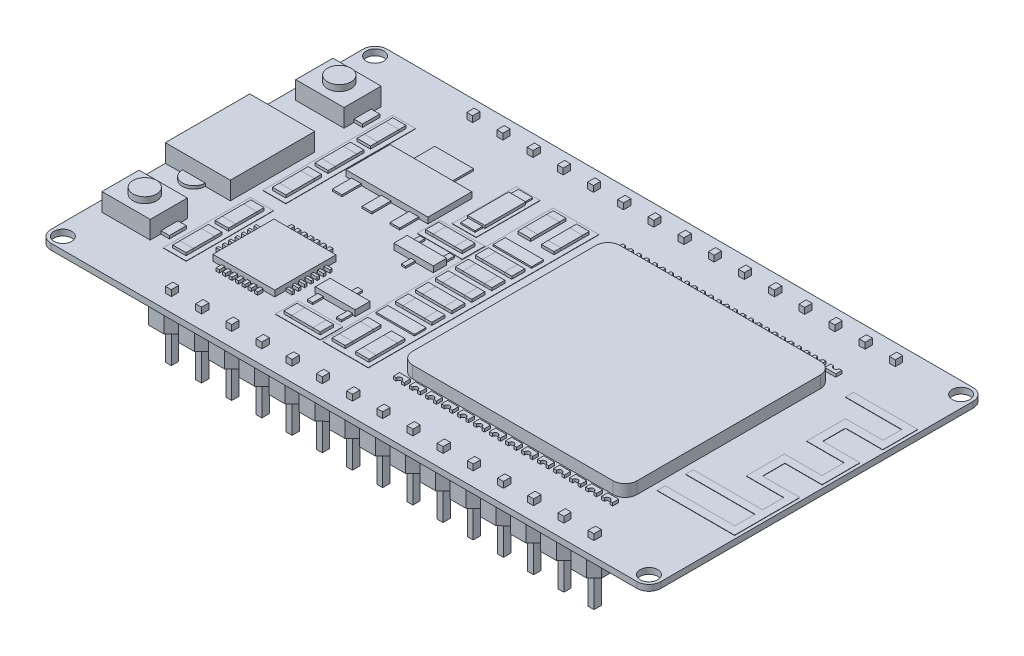
SolidWorks part; units mm, degrees
ref_plane "Front Plane" through (0, 0, 0) normal (0, 0, 1) x (1, 0, 0)
ref_plane "Top Plane" through (0, 0, 0) normal (0, 1, 0) x (1, 0, 0)
ref_plane "Right Plane" through (0, 0, 0) normal (1, 0, 0) x (0, 0, -1)
sketch "Sketch1" plane through (0, 0, 0) normal (0, 1, 0) x (1, 0, 0)
  line L0 (166.6667, 275.5) -> (833.3333, 275.5) construction
sketch "Sketch2" plane through (0, 0, 0) normal (0, 1, 0) x (1, 0, 0)
  line L1 (0, 0) -> (25.5, 0)
  line L2 (0, 0) -> (0, 14.05)
  line L3 (0, 14.05) -> (25.5, 14.05)
  line L4 (25.5, 0) -> (25.5, 14.05)
  dimension "D1" = 14.05
  dimension "D2" = 25.5
extrude "Boss-Extrude1" add sketch "Sketch2" against normal blind 0.5
fillet "Fillet3" radius 1 1 edges at (0, -0.25, 0)
sketch "Sketch3" plane through (0, 0, 0) normal (0, 1, 0) x (1, 0, 0)
  line L0 (0.2929, 0.2929) -> (1, 1) construction
  arc A0 (0, 1) -> (1, 0) centre (1, 1) ccw construction
  circle A1 centre (1, 1) radius 0.7368
extrude "Cut-Extrude1" cut sketch "Sketch3" along normal up to surface (-0.5 mm away) up to face at (10.3586, -0.5, -5.7786)
mirror "Mirror1" about plane through (25.5, -0.5, 0) normal (1, 0, 0) of bodies 102
mirror "Mirror2" about plane through (0, -0.5, -14.05) normal (0, 0, -1) of bodies 103
sketch "Sketch4" plane through (0, 0, 0) normal (0, 1, 0) x (1, 0, 0)
  line L1 (25.9436, 22.6267) -> (42.7039, 22.6267)
  line L2 (24.9436, 21.6267) -> (24.9436, 6.2994)
  line L3 (25.9436, 5.2994) -> (42.7039, 5.2994)
  line L4 (43.7039, 21.6267) -> (43.7039, 6.2994)
  arc A0 (24.9436, 6.2994) -> (25.9436, 5.2994) centre (25.9436, 6.2994) ccw
  arc A1 (42.7039, 5.2994) -> (43.7039, 6.2994) centre (42.7039, 6.2994) ccw
  arc A2 (42.7039, 22.6267) -> (43.7039, 21.6267) centre (42.7039, 21.6267) cw
  arc A3 (25.9436, 22.6267) -> (24.9436, 21.6267) centre (25.9436, 21.6267) ccw
  dimension "D1" = 1
extrude "Boss-Extrude2" add sketch "Sketch4" along normal blind 1 separate body
sketch "Sketch5" plane through (0, 0, 0) normal (0, 1, 0) x (1, 0, 0)
  line L0 (24.7912, 7.6997) -> (24.2806, 7.6997)
  line L1 (24.2806, 7.6997) -> (24.2806, 7.8949)
  line L2 (24.7912, 7.6997) -> (24.7912, 8.5161)
  line L4 (24.2806, 8.5161) -> (24.2806, 8.3221)
  line L5 (24.7912, 8.5161) -> (24.2806, 8.5161)
  line L6 (24.2806, 9.8562) -> (24.2806, 9.6622)
  line L7 (24.7912, 9.8562) -> (24.2806, 9.8562)
  line L8 (24.7912, 9.0397) -> (24.7912, 9.8562)
  line L9 (24.7912, 9.0397) -> (24.2806, 9.0397)
  line L10 (24.2806, 9.0397) -> (24.2806, 9.235)
  line L11 (24.2806, 11.1963) -> (24.2806, 11.0023)
  line L12 (24.7912, 11.1963) -> (24.2806, 11.1963)
  line L13 (24.7912, 10.3798) -> (24.7912, 11.1963)
  line L14 (24.7912, 10.3798) -> (24.2806, 10.3798)
  line L15 (24.2806, 10.3798) -> (24.2806, 10.575)
  line L16 (24.2806, 12.5363) -> (24.2806, 12.3423)
  line L17 (24.7912, 12.5363) -> (24.2806, 12.5363)
  line L18 (24.7912, 11.7199) -> (24.7912, 12.5363)
  line L19 (24.7912, 11.7199) -> (24.2806, 11.7199)
  line L20 (24.2806, 11.7199) -> (24.2806, 11.9151)
  line L21 (24.2806, 13.8764) -> (24.2806, 13.6824)
  line L22 (24.7912, 13.8764) -> (24.2806, 13.8764)
  line L23 (24.7912, 13.06) -> (24.7912, 13.8764)
  line L24 (24.7912, 13.06) -> (24.2806, 13.06)
  line L25 (24.2806, 13.06) -> (24.2806, 13.2552)
  line L26 (24.2806, 15.2165) -> (24.2806, 15.0225)
  line L27 (24.7912, 15.2165) -> (24.2806, 15.2165)
  line L28 (24.7912, 14.4) -> (24.7912, 15.2165)
  line L29 (24.7912, 14.4) -> (24.2806, 14.4)
  line L30 (24.2806, 14.4) -> (24.2806, 14.5953)
  line L31 (24.2806, 16.5566) -> (24.2806, 16.3626)
  line L32 (24.7912, 16.5566) -> (24.2806, 16.5566)
  line L33 (24.7912, 15.7401) -> (24.7912, 16.5566)
  line L34 (24.7912, 15.7401) -> (24.2806, 15.7401)
  line L35 (24.2806, 15.7401) -> (24.2806, 15.9353)
  line L36 (24.2806, 17.8967) -> (24.2806, 17.7026)
  line L37 (24.7912, 17.8967) -> (24.2806, 17.8967)
  line L38 (24.7912, 17.0802) -> (24.7912, 17.8967)
  line L39 (24.7912, 17.0802) -> (24.2806, 17.0802)
  line L40 (24.2806, 17.0802) -> (24.2806, 17.2754)
  line L41 (24.2806, 19.2367) -> (24.2806, 19.0427)
  line L42 (24.7912, 19.2367) -> (24.2806, 19.2367)
  line L43 (24.7912, 18.4203) -> (24.7912, 19.2367)
  line L44 (24.7912, 18.4203) -> (24.2806, 18.4203)
  line L45 (24.2806, 18.4203) -> (24.2806, 18.6155)
  line L46 (24.2806, 20.5768) -> (24.2806, 20.3828)
  line L47 (24.7912, 20.5768) -> (24.2806, 20.5768)
  line L48 (24.7912, 19.7603) -> (24.7912, 20.5768)
  line L49 (24.7912, 19.7603) -> (24.2806, 19.7603)
  line L50 (24.2806, 19.7603) -> (24.2806, 19.9556)
  line L51 (25.1907, 23.6105) -> (25.1907, 23.1041)
  line L52 (25.1907, 23.1041) -> (26.111, 23.1041)
  line L54 (25.1907, 23.6105) -> (25.4208, 23.6105)
  line L55 (26.111, 23.6105) -> (26.111, 23.1041)
  line L56 (26.111, 23.6105) -> (25.8809, 23.6105)
  line L57 (26.5297, 23.1041) -> (27.45, 23.1041)
  line L58 (27.45, 23.6105) -> (27.45, 23.1041)
  line L59 (27.45, 23.6105) -> (27.2199, 23.6105)
  line L60 (26.5297, 23.6105) -> (26.7598, 23.6105)
  line L61 (26.5297, 23.6105) -> (26.5297, 23.1041)
  line L62 (27.8686, 23.1041) -> (28.7889, 23.1041)
  line L63 (28.7889, 23.6105) -> (28.7889, 23.1041)
  line L64 (28.7889, 23.6105) -> (28.5589, 23.6105)
  line L65 (27.8686, 23.6105) -> (28.0987, 23.6105)
  line L66 (27.8686, 23.6105) -> (27.8686, 23.1041)
  line L67 (29.2076, 23.1041) -> (30.1279, 23.1041)
  line L68 (30.1279, 23.6105) -> (30.1279, 23.1041)
  line L69 (30.1279, 23.6105) -> (29.8978, 23.6105)
  line L70 (29.2076, 23.6105) -> (29.4377, 23.6105)
  line L71 (29.2076, 23.6105) -> (29.2076, 23.1041)
  line L72 (30.5466, 23.1041) -> (31.4669, 23.1041)
  line L73 (31.4669, 23.6105) -> (31.4669, 23.1041)
  line L74 (31.4669, 23.6105) -> (31.2368, 23.6105)
  line L75 (30.5466, 23.6105) -> (30.7766, 23.6105)
  line L76 (30.5466, 23.6105) -> (30.5466, 23.1041)
  line L77 (31.8855, 23.1041) -> (32.8058, 23.1041)
  line L78 (32.8058, 23.6105) -> (32.8058, 23.1041)
  line L79 (32.8058, 23.6105) -> (32.5758, 23.6105)
  line L80 (31.8855, 23.6105) -> (32.1156, 23.6105)
  line L81 (31.8855, 23.6105) -> (31.8855, 23.1041)
  line L82 (33.2245, 23.1041) -> (34.1448, 23.1041)
  line L83 (34.1448, 23.6105) -> (34.1448, 23.1041)
  line L84 (34.1448, 23.6105) -> (33.9147, 23.6105)
  line L85 (33.2245, 23.6105) -> (33.4546, 23.6105)
  line L86 (33.2245, 23.6105) -> (33.2245, 23.1041)
  line L87 (34.5635, 23.1041) -> (35.4838, 23.1041)
  line L88 (35.4838, 23.6105) -> (35.4838, 23.1041)
  line L89 (35.4838, 23.6105) -> (35.2537, 23.6105)
  line L90 (34.5635, 23.6105) -> (34.7935, 23.6105)
  line L91 (34.5635, 23.6105) -> (34.5635, 23.1041)
  line L92 (35.9024, 23.1041) -> (36.8227, 23.1041)
  line L93 (36.8227, 23.6105) -> (36.8227, 23.1041)
  line L94 (36.8227, 23.6105) -> (36.5926, 23.6105)
  line L95 (35.9024, 23.6105) -> (36.1325, 23.6105)
  line L96 (35.9024, 23.6105) -> (35.9024, 23.1041)
  line L97 (37.2414, 23.1041) -> (38.1617, 23.1041)
  line L98 (38.1617, 23.6105) -> (38.1617, 23.1041)
  line L99 (38.1617, 23.6105) -> (37.9316, 23.6105)
  line L100 (37.2414, 23.6105) -> (37.4715, 23.6105)
  line L101 (37.2414, 23.6105) -> (37.2414, 23.1041)
  line L102 (38.5803, 23.1041) -> (39.5006, 23.1041)
  line L103 (39.5006, 23.6105) -> (39.5006, 23.1041)
  line L104 (39.5006, 23.6105) -> (39.2706, 23.6105)
  line L105 (38.5803, 23.6105) -> (38.8104, 23.6105)
  line L106 (38.5803, 23.6105) -> (38.5803, 23.1041)
  line L107 (39.9193, 23.1041) -> (40.8396, 23.1041)
  line L108 (40.8396, 23.6105) -> (40.8396, 23.1041)
  line L109 (40.8396, 23.6105) -> (40.6095, 23.6105)
  line L110 (39.9193, 23.6105) -> (40.1494, 23.6105)
  line L111 (39.9193, 23.6105) -> (39.9193, 23.1041)
  line L112 (41.2583, 23.1041) -> (42.1786, 23.1041)
  line L113 (42.1786, 23.6105) -> (42.1786, 23.1041)
  line L114 (42.1786, 23.6105) -> (41.9485, 23.6105)
  line L115 (41.2583, 23.6105) -> (41.4883, 23.6105)
  line L116 (41.2583, 23.6105) -> (41.2583, 23.1041)
  line L117 (42.5972, 23.1041) -> (43.5175, 23.1041)
  line L118 (43.5175, 23.6105) -> (43.5175, 23.1041)
  line L119 (43.5175, 23.6105) -> (43.2875, 23.6105)
  line L120 (42.5972, 23.6105) -> (42.8273, 23.6105)
  line L121 (42.5972, 23.6105) -> (42.5972, 23.1041)
  line L123 (24.7912, 14.0286) -> (43.0574, 14.0286) construction
  line L124 (35.9024, 4.4466) -> (35.9024, 4.953)
  line L125 (35.9024, 4.4466) -> (36.1325, 4.4466)
  line L126 (36.8227, 4.4466) -> (36.5926, 4.4466)
  line L127 (36.8227, 4.4466) -> (36.8227, 4.953)
  line L128 (35.9024, 4.953) -> (36.8227, 4.953)
  line L129 (37.2414, 4.4466) -> (37.2414, 4.953)
  line L130 (37.2414, 4.4466) -> (37.4715, 4.4466)
  line L131 (38.1617, 4.4466) -> (37.9316, 4.4466)
  line L132 (38.1617, 4.4466) -> (38.1617, 4.953)
  line L133 (37.2414, 4.953) -> (38.1617, 4.953)
  line L134 (38.5803, 4.4466) -> (38.5803, 4.953)
  line L135 (38.5803, 4.4466) -> (38.8104, 4.4466)
  line L136 (39.5006, 4.4466) -> (39.2706, 4.4466)
  line L137 (39.5006, 4.4466) -> (39.5006, 4.953)
  line L138 (38.5803, 4.953) -> (39.5006, 4.953)
  line L139 (39.9193, 4.4466) -> (39.9193, 4.953)
  line L140 (39.9193, 4.4466) -> (40.1494, 4.4466)
  line L141 (40.8396, 4.4466) -> (40.6095, 4.4466)
  line L142 (40.8396, 4.4466) -> (40.8396, 4.953)
  line L143 (39.9193, 4.953) -> (40.8396, 4.953)
  line L144 (41.2583, 4.4466) -> (41.2583, 4.953)
  line L145 (41.2583, 4.4466) -> (41.4883, 4.4466)
  line L146 (42.1786, 4.4466) -> (41.9485, 4.4466)
  line L147 (42.1786, 4.4466) -> (42.1786, 4.953)
  line L148 (41.2583, 4.953) -> (42.1786, 4.953)
  line L149 (42.5972, 4.4466) -> (42.5972, 4.953)
  line L150 (42.5972, 4.4466) -> (42.8273, 4.4466)
  line L151 (43.5175, 4.4466) -> (43.2875, 4.4466)
  line L152 (43.5175, 4.4466) -> (43.5175, 4.953)
  line L153 (42.5972, 4.953) -> (43.5175, 4.953)
  line L154 (34.5635, 4.4466) -> (34.5635, 4.953)
  line L155 (34.5635, 4.4466) -> (34.7935, 4.4466)
  line L156 (35.4838, 4.4466) -> (35.2537, 4.4466)
  line L157 (35.4838, 4.4466) -> (35.4838, 4.953)
  line L158 (34.5635, 4.953) -> (35.4838, 4.953)
  line L159 (33.2245, 4.4466) -> (33.2245, 4.953)
  line L160 (33.2245, 4.4466) -> (33.4546, 4.4466)
  line L161 (34.1448, 4.4466) -> (33.9147, 4.4466)
  line L162 (34.1448, 4.4466) -> (34.1448, 4.953)
  line L163 (33.2245, 4.953) -> (34.1448, 4.953)
  line L164 (31.8855, 4.4466) -> (31.8855, 4.953)
  line L165 (31.8855, 4.4466) -> (32.1156, 4.4466)
  line L166 (32.8058, 4.4466) -> (32.5758, 4.4466)
  line L167 (32.8058, 4.4466) -> (32.8058, 4.953)
  line L168 (31.8855, 4.953) -> (32.8058, 4.953)
  line L169 (30.5466, 4.4466) -> (30.5466, 4.953)
  line L170 (30.5466, 4.4466) -> (30.7766, 4.4466)
  line L171 (31.4669, 4.4466) -> (31.2368, 4.4466)
  line L172 (31.4669, 4.4466) -> (31.4669, 4.953)
  line L173 (30.5466, 4.953) -> (31.4669, 4.953)
  line L174 (29.2076, 4.4466) -> (29.2076, 4.953)
  line L175 (29.2076, 4.4466) -> (29.4377, 4.4466)
  line L176 (30.1279, 4.4466) -> (29.8978, 4.4466)
  line L177 (30.1279, 4.4466) -> (30.1279, 4.953)
  line L178 (29.2076, 4.953) -> (30.1279, 4.953)
  line L179 (27.8686, 4.4466) -> (27.8686, 4.953)
  line L180 (27.8686, 4.4466) -> (28.0987, 4.4466)
  line L181 (28.7889, 4.4466) -> (28.5589, 4.4466)
  line L182 (28.7889, 4.4466) -> (28.7889, 4.953)
  line L183 (27.8686, 4.953) -> (28.7889, 4.953)
  line L184 (26.5297, 4.4466) -> (26.5297, 4.953)
  line L185 (26.5297, 4.4466) -> (26.7598, 4.4466)
  line L186 (27.45, 4.4466) -> (27.2199, 4.4466)
  line L187 (27.45, 4.4466) -> (27.45, 4.953)
  line L188 (26.5297, 4.953) -> (27.45, 4.953)
  line L189 (25.1907, 4.4466) -> (25.1907, 4.953)
  line L190 (25.1907, 4.4466) -> (25.4208, 4.4466)
  line L191 (26.111, 4.4466) -> (25.8809, 4.4466)
  line L192 (26.111, 4.4466) -> (26.111, 4.953)
  line L193 (25.1907, 4.953) -> (26.111, 4.953)
  arc A0 (24.2806, 7.8949) -> (24.2806, 8.3221) centre (24.2806, 8.1085) ccw
  arc A1 (24.2806, 9.235) -> (24.2806, 9.6622) centre (24.2806, 9.4486) ccw
  arc A2 (24.2806, 10.575) -> (24.2806, 11.0023) centre (24.2806, 10.7886) ccw
  arc A3 (24.2806, 11.9151) -> (24.2806, 12.3423) centre (24.2806, 12.1287) ccw
  arc A4 (24.2806, 13.2552) -> (24.2806, 13.6824) centre (24.2806, 13.4688) ccw
  arc A5 (24.2806, 14.5953) -> (24.2806, 15.0225) centre (24.2806, 14.8089) ccw
  arc A6 (24.2806, 15.9353) -> (24.2806, 16.3626) centre (24.2806, 16.149) ccw
  arc A7 (24.2806, 17.2754) -> (24.2806, 17.7026) centre (24.2806, 17.489) ccw
  arc A8 (24.2806, 18.6155) -> (24.2806, 19.0427) centre (24.2806, 18.8291) ccw
  arc A9 (24.2806, 19.9556) -> (24.2806, 20.3828) centre (24.2806, 20.1692) ccw
  arc A10 (25.4208, 23.6105) -> (25.8809, 23.6105) centre (25.6509, 23.6105) ccw
  arc A11 (26.7598, 23.6105) -> (27.2199, 23.6105) centre (26.9898, 23.6105) ccw
  arc A12 (28.0987, 23.6105) -> (28.5589, 23.6105) centre (28.3288, 23.6105) ccw
  arc A13 (29.4377, 23.6105) -> (29.8978, 23.6105) centre (29.6678, 23.6105) ccw
  arc A14 (30.7766, 23.6105) -> (31.2368, 23.6105) centre (31.0067, 23.6105) ccw
  arc A15 (32.1156, 23.6105) -> (32.5758, 23.6105) centre (32.3457, 23.6105) ccw
  arc A16 (33.4546, 23.6105) -> (33.9147, 23.6105) centre (33.6846, 23.6105) ccw
  arc A17 (34.7935, 23.6105) -> (35.2537, 23.6105) centre (35.0236, 23.6105) ccw
  arc A18 (36.1325, 23.6105) -> (36.5926, 23.6105) centre (36.3626, 23.6105) ccw
  arc A19 (37.4715, 23.6105) -> (37.9316, 23.6105) centre (37.7015, 23.6105) ccw
  arc A20 (38.8104, 23.6105) -> (39.2706, 23.6105) centre (39.0405, 23.6105) ccw
  arc A21 (40.1494, 23.6105) -> (40.6095, 23.6105) centre (40.3795, 23.6105) ccw
  arc A22 (41.4883, 23.6105) -> (41.9485, 23.6105) centre (41.7184, 23.6105) ccw
  arc A23 (42.8273, 23.6105) -> (43.2875, 23.6105) centre (43.0574, 23.6105) ccw
  arc A24 (36.1325, 4.4466) -> (36.5926, 4.4466) centre (36.3626, 4.4466) cw
  arc A25 (37.4715, 4.4466) -> (37.9316, 4.4466) centre (37.7015, 4.4466) cw
  arc A26 (38.8104, 4.4466) -> (39.2706, 4.4466) centre (39.0405, 4.4466) cw
  arc A27 (40.1494, 4.4466) -> (40.6095, 4.4466) centre (40.3795, 4.4466) cw
  arc A28 (41.4883, 4.4466) -> (41.9485, 4.4466) centre (41.7184, 4.4466) cw
  arc A29 (42.8273, 4.4466) -> (43.2875, 4.4466) centre (43.0574, 4.4466) cw
  arc A30 (34.7935, 4.4466) -> (35.2537, 4.4466) centre (35.0236, 4.4466) cw
  arc A31 (33.4546, 4.4466) -> (33.9147, 4.4466) centre (33.6846, 4.4466) cw
  arc A32 (32.1156, 4.4466) -> (32.5758, 4.4466) centre (32.3457, 4.4466) cw
  arc A33 (30.7766, 4.4466) -> (31.2368, 4.4466) centre (31.0067, 4.4466) cw
  arc A34 (29.4377, 4.4466) -> (29.8978, 4.4466) centre (29.6678, 4.4466) cw
  arc A35 (28.0987, 4.4466) -> (28.5589, 4.4466) centre (28.3288, 4.4466) cw
  arc A36 (26.7598, 4.4466) -> (27.2199, 4.4466) centre (26.9898, 4.4466) cw
  arc A37 (25.4208, 4.4466) -> (25.8809, 4.4466) centre (25.6509, 4.4466) cw
  dimension "D1" = 10
  dimension "D2" = 14
extrude "Boss-Extrude3" add sketch "Sketch5" along normal blind 0.25 separate body
sketch "Sketch6" plane through (0, 0, 0) normal (0, 1, 0) x (1, 0, 0)
  line L1 (9.0736, 10.5768) -> (14.253, 10.5768)
  line L2 (9.0736, 10.5768) -> (9.0736, 5.4648)
  line L3 (9.0736, 5.4648) -> (14.253, 5.4648)
  line L4 (14.253, 10.5768) -> (14.253, 5.4648)
extrude "Boss-Extrude4" add sketch "Sketch6" along normal blind 0.5 separate body
sketch "Sketch7" plane through (0, 0, 0) normal (0, 1, 0) x (1, 0, 0)
  line L0 (14.3341, 7.051) -> (14.3341, 6.8485)
  line L1 (14.3341, 6.525) -> (14.8378, 6.525)
  line L2 (14.3341, 6.525) -> (14.3341, 6.3225)
  line L3 (14.3341, 6.3225) -> (14.8378, 6.3225)
  line L4 (14.8378, 6.525) -> (14.8378, 6.3225)
  line L5 (14.3341, 7.051) -> (14.8378, 7.051)
  line L6 (14.8378, 7.051) -> (14.8378, 6.8485)
  line L7 (14.3341, 6.8485) -> (14.8378, 6.8485)
  line L8 (14.3341, 7.5771) -> (14.3341, 7.3746)
  line L9 (14.3341, 7.5771) -> (14.8378, 7.5771)
  line L10 (14.8378, 7.5771) -> (14.8378, 7.3746)
  line L11 (14.3341, 7.3746) -> (14.8378, 7.3746)
  line L12 (14.3341, 8.1031) -> (14.3341, 7.9006)
  line L13 (14.3341, 8.1031) -> (14.8378, 8.1031)
  line L14 (14.8378, 8.1031) -> (14.8378, 7.9006)
  line L15 (14.3341, 7.9006) -> (14.8378, 7.9006)
  line L16 (14.3341, 8.6292) -> (14.3341, 8.4267)
  line L17 (14.3341, 8.6292) -> (14.8378, 8.6292)
  line L18 (14.8378, 8.6292) -> (14.8378, 8.4267)
  line L19 (14.3341, 8.4267) -> (14.8378, 8.4267)
  line L20 (14.3341, 9.1552) -> (14.3341, 8.9527)
  line L21 (14.3341, 9.1552) -> (14.8378, 9.1552)
  line L22 (14.8378, 9.1552) -> (14.8378, 8.9527)
  line L23 (14.3341, 8.9527) -> (14.8378, 8.9527)
  line L24 (14.3341, 9.6813) -> (14.3341, 9.4788)
  line L25 (14.3341, 9.6813) -> (14.8378, 9.6813)
  line L26 (14.8378, 9.6813) -> (14.8378, 9.4788)
  line L27 (14.3341, 9.4788) -> (14.8378, 9.4788)
  line L28 (11.6633, 10.5768) -> (11.6633, 5.4648) construction
  line L29 (14.253, 10.5768) -> (9.0736, 10.5768) construction
  line L30 (9.0736, 5.4648) -> (14.253, 5.4648) construction
  line L31 (8.9924, 6.3225) -> (8.4887, 6.3225)
  line L32 (8.4887, 6.525) -> (8.4887, 6.3225)
  line L33 (8.9924, 6.525) -> (8.4887, 6.525)
  line L34 (8.9924, 6.525) -> (8.9924, 6.3225)
  line L35 (8.9924, 7.051) -> (8.4887, 7.051)
  line L36 (8.4887, 7.051) -> (8.4887, 6.8485)
  line L37 (8.9924, 6.8485) -> (8.4887, 6.8485)
  line L38 (8.9924, 7.051) -> (8.9924, 6.8485)
  line L39 (8.9924, 7.5771) -> (8.4887, 7.5771)
  line L40 (8.4887, 7.5771) -> (8.4887, 7.3746)
  line L41 (8.9924, 7.3746) -> (8.4887, 7.3746)
  line L42 (8.9924, 7.5771) -> (8.9924, 7.3746)
  line L43 (8.9924, 8.1031) -> (8.4887, 8.1031)
  line L44 (8.4887, 8.1031) -> (8.4887, 7.9006)
  line L45 (8.9924, 7.9006) -> (8.4887, 7.9006)
  line L46 (8.9924, 8.1031) -> (8.9924, 7.9006)
  line L47 (8.9924, 8.6292) -> (8.4887, 8.6292)
  line L48 (8.4887, 8.6292) -> (8.4887, 8.4267)
  line L49 (8.9924, 8.4267) -> (8.4887, 8.4267)
  line L50 (8.9924, 8.6292) -> (8.9924, 8.4267)
  line L51 (8.9924, 9.1552) -> (8.4887, 9.1552)
  line L52 (8.4887, 9.1552) -> (8.4887, 8.9527)
  line L53 (8.9924, 8.9527) -> (8.4887, 8.9527)
  line L54 (8.9924, 9.1552) -> (8.9924, 8.9527)
  line L55 (8.9924, 9.6813) -> (8.4887, 9.6813)
  line L56 (8.4887, 9.6813) -> (8.4887, 9.4788)
  line L57 (8.9924, 9.4788) -> (8.4887, 9.4788)
  line L58 (8.9924, 9.6813) -> (8.9924, 9.4788)
  line L59 (10.4789, 11.1679) -> (10.4789, 10.7079)
  line L60 (9.9436, 11.1677) -> (10.2062, 11.1677)
  line L61 (9.9436, 11.1677) -> (9.9436, 10.7078)
  line L62 (9.9436, 10.7078) -> (10.2062, 10.7078)
  line L63 (10.2062, 11.1677) -> (10.2062, 10.7078)
  line L64 (10.4789, 11.1679) -> (10.7415, 11.1679)
  line L65 (10.7415, 11.1679) -> (10.7415, 10.7079)
  line L66 (10.4789, 10.7079) -> (10.7415, 10.7079)
  line L67 (11.0142, 11.168) -> (11.0142, 10.708)
  line L68 (11.0142, 11.168) -> (11.2768, 11.168)
  line L69 (11.2768, 11.168) -> (11.2768, 10.708)
  line L70 (11.0142, 10.708) -> (11.2768, 10.708)
  line L71 (11.5496, 11.1681) -> (11.5496, 10.7082)
  line L72 (11.5496, 11.1681) -> (11.8121, 11.1681)
  line L73 (11.8121, 11.1681) -> (11.8121, 10.7082)
  line L74 (11.5496, 10.7082) -> (11.8121, 10.7082)
  line L75 (12.0849, 11.1682) -> (12.0849, 10.7083)
  line L76 (12.0849, 11.1682) -> (12.3474, 11.1682)
  line L77 (12.3474, 11.1682) -> (12.3474, 10.7083)
  line L78 (12.0849, 10.7083) -> (12.3474, 10.7083)
  line L79 (12.6202, 11.1683) -> (12.6202, 10.7084)
  line L80 (12.6202, 11.1683) -> (12.8827, 11.1683)
  line L81 (12.8827, 11.1683) -> (12.8827, 10.7084)
  line L82 (12.6202, 10.7084) -> (12.8827, 10.7084)
  line L83 (13.1555, 11.1685) -> (13.1555, 10.7085)
  line L84 (13.1555, 11.1685) -> (13.418, 11.1685)
  line L85 (13.418, 11.1685) -> (13.418, 10.7085)
  line L86 (13.1555, 10.7085) -> (13.418, 10.7085)
  line L87 (9.0736, 8.0208) -> (14.253, 8.0208) construction
  line L88 (9.0736, 10.5768) -> (9.0736, 5.4648) construction
  line L89 (14.253, 5.4648) -> (14.253, 10.5768) construction
  line L90 (13.1555, 4.8732) -> (13.418, 4.8732)
  line L91 (13.418, 4.8732) -> (13.418, 5.3331)
  line L92 (13.1555, 5.3331) -> (13.418, 5.3331)
  line L93 (13.1555, 4.8732) -> (13.1555, 5.3331)
  line L94 (12.6202, 4.8733) -> (12.8827, 4.8733)
  line L95 (12.8827, 4.8733) -> (12.8827, 5.3333)
  line L96 (12.6202, 5.3333) -> (12.8827, 5.3333)
  line L97 (12.6202, 4.8733) -> (12.6202, 5.3333)
  line L98 (12.0849, 4.8734) -> (12.3474, 4.8734)
  line L99 (12.3474, 4.8734) -> (12.3474, 5.3334)
  line L100 (12.0849, 5.3334) -> (12.3474, 5.3334)
  line L101 (12.0849, 4.8734) -> (12.0849, 5.3334)
  line L102 (11.5496, 4.8736) -> (11.8121, 4.8736)
  line L103 (11.8121, 4.8736) -> (11.8121, 5.3335)
  line L104 (11.5496, 5.3335) -> (11.8121, 5.3335)
  line L105 (11.5496, 4.8736) -> (11.5496, 5.3335)
  line L106 (11.0142, 4.8737) -> (11.2768, 4.8737)
  line L107 (11.2768, 4.8737) -> (11.2768, 5.3336)
  line L108 (11.0142, 5.3336) -> (11.2768, 5.3336)
  line L109 (11.0142, 4.8737) -> (11.0142, 5.3336)
  line L110 (10.4789, 4.8738) -> (10.7415, 4.8738)
  line L111 (10.7415, 4.8738) -> (10.7415, 5.3337)
  line L112 (10.4789, 5.3337) -> (10.7415, 5.3337)
  line L113 (10.4789, 4.8738) -> (10.4789, 5.3337)
  line L114 (9.9436, 5.3339) -> (10.2062, 5.3339)
  line L115 (10.2062, 4.8739) -> (10.2062, 5.3339)
  line L116 (9.9436, 4.8739) -> (10.2062, 4.8739)
  line L117 (9.9436, 4.8739) -> (9.9436, 5.3339)
  dimension "D1" = 7
  dimension "D2" = 7
extrude "Boss-Extrude5" add sketch "Sketch7" along normal blind 0.25 separate body
sketch "Sketch8" plane through (0, 0, 0) normal (0, 1, 0) x (1, 0, 0)
  line L0 (22.2898, 12.7032) -> (22.2898, 11.6145)
  line L1 (15.8874, 5.6953) -> (16.5367, 5.6953)
  line L2 (15.8874, 5.6953) -> (15.8874, 4.587)
  line L3 (15.8874, 4.587) -> (16.5367, 4.587)
  line L4 (16.5367, 5.6953) -> (16.5367, 4.587)
  line L5 (19.859, 5.2465) -> (20.9619, 5.2465)
  line L6 (18.3166, 5.6953) -> (18.9258, 5.6953)
  line L7 (18.3166, 5.6953) -> (18.3166, 4.587)
  line L8 (18.3166, 4.587) -> (18.9258, 4.587)
  line L9 (18.9258, 5.6953) -> (18.9258, 4.587)
  line L10 (19.859, 5.2465) -> (19.859, 4.645)
  line L11 (19.859, 4.645) -> (20.9619, 4.645)
  line L12 (20.9619, 5.2465) -> (20.9619, 4.645)
  line L13 (21.8334, 7.6373) -> (22.9516, 7.6373)
  line L14 (19.859, 7.0126) -> (20.9619, 7.0126)
  line L15 (19.859, 7.0126) -> (19.859, 7.6373)
  line L16 (19.859, 7.6373) -> (20.9619, 7.6373)
  line L17 (20.9619, 7.0126) -> (20.9619, 7.6373)
  line L18 (21.8334, 7.6373) -> (21.8334, 7.0126)
  line L19 (21.8334, 7.0126) -> (22.9516, 7.0126)
  line L20 (22.9516, 7.6373) -> (22.9516, 7.0126)
  line L21 (21.8334, 5.2465) -> (22.9516, 5.2465)
  line L22 (21.8334, 5.2465) -> (21.8334, 4.645)
  line L23 (21.8334, 4.645) -> (22.9516, 4.645)
  line L24 (22.9516, 5.2465) -> (22.9516, 4.645)
  line L25 (22.2898, 11.0323) -> (22.9048, 11.0323)
  line L26 (22.2898, 11.0323) -> (22.2898, 9.9437)
  line L27 (22.2898, 9.9437) -> (22.9048, 9.9437)
  line L28 (22.9048, 11.0323) -> (22.9048, 9.9437)
  line L29 (22.2898, 12.7032) -> (22.9048, 12.7032)
  line L30 (22.9048, 12.7032) -> (22.9048, 11.6145)
  line L31 (22.2898, 11.6145) -> (22.9048, 11.6145)
  line L32 (22.2898, 14.374) -> (22.2898, 13.2853)
  line L33 (22.2898, 14.374) -> (22.9048, 14.374)
  line L34 (22.9048, 14.374) -> (22.9048, 13.2853)
  line L35 (22.2898, 13.2853) -> (22.9048, 13.2853)
  line L36 (22.2898, 16.0448) -> (22.2898, 14.9561)
  line L37 (22.2898, 16.0448) -> (22.9048, 16.0448)
  line L38 (22.9048, 16.0448) -> (22.9048, 14.9561)
  line L39 (22.2898, 14.9561) -> (22.9048, 14.9561)
  line L40 (22.2898, 17.7156) -> (22.2898, 16.627)
  line L41 (22.2898, 17.7156) -> (22.9048, 17.7156)
  line L42 (22.9048, 17.7156) -> (22.9048, 16.627)
  line L43 (22.2898, 16.627) -> (22.9048, 16.627)
  line L44 (19.8598, 12.7032) -> (19.8598, 11.6145)
  line L45 (19.8598, 12.7032) -> (20.4747, 12.7032)
  line L46 (20.4747, 12.7032) -> (20.4747, 11.6145)
  line L47 (19.8598, 11.6145) -> (20.4747, 11.6145)
  line L48 (19.8598, 14.374) -> (19.8598, 13.2853)
  line L49 (19.8598, 14.374) -> (20.4747, 14.374)
  line L50 (20.4747, 14.374) -> (20.4747, 13.2853)
  line L51 (19.8598, 13.2853) -> (20.4747, 13.2853)
  line L52 (19.8598, 16.0448) -> (19.8598, 14.9561)
  line L53 (19.8598, 16.0448) -> (20.4747, 16.0448)
  line L54 (20.4747, 16.0448) -> (20.4747, 14.9561)
  line L55 (19.8598, 14.9561) -> (20.4747, 14.9561)
  line L56 (19.8598, 17.7156) -> (19.8598, 16.627)
  line L57 (19.8598, 17.7156) -> (20.4747, 17.7156)
  line L58 (20.4747, 17.7156) -> (20.4747, 16.627)
  line L59 (19.8598, 16.627) -> (20.4747, 16.627)
  line L60 (19.8598, 11.0323) -> (19.8598, 9.9437)
  line L61 (19.8598, 11.0323) -> (20.4747, 11.0323)
  line L62 (20.4747, 11.0323) -> (20.4747, 9.9437)
  line L63 (19.8598, 9.9437) -> (20.4747, 9.9437)
  line L64 (6.4677, 11.2462) -> (6.4677, 10.6509)
  line L65 (6.4677, 7.6997) -> (7.5831, 7.6997)
  line L66 (6.4677, 7.6997) -> (6.4677, 7.1044)
  line L67 (6.4677, 7.1044) -> (7.5831, 7.1044)
  line L68 (7.5831, 7.6997) -> (7.5831, 7.1044)
  line L69 (6.4677, 5.3185) -> (7.5831, 5.3185)
  line L70 (6.4677, 5.3185) -> (6.4677, 4.7164)
  line L71 (6.4677, 4.7164) -> (7.5831, 4.7164)
  line L72 (7.5831, 5.3185) -> (7.5831, 4.7164)
  line L73 (6.4677, 11.2462) -> (7.5831, 11.2462)
  line L74 (7.5831, 11.2462) -> (7.5831, 10.6509)
  line L75 (6.4677, 10.6509) -> (7.5831, 10.6509)
  line L76 (6.4677, 8.865) -> (6.4677, 8.2628)
  line L77 (6.4677, 8.865) -> (7.5831, 8.865)
  line L78 (7.5831, 8.865) -> (7.5831, 8.2628)
  line L79 (6.4677, 8.2628) -> (7.5831, 8.2628)
  line L80 (6.4558, 16.0476) -> (6.4558, 15.4523)
  line L81 (6.4558, 16.0476) -> (7.5711, 16.0476)
  line L82 (7.5711, 16.0476) -> (7.5711, 15.4523)
  line L83 (6.4558, 15.4523) -> (7.5711, 15.4523)
  line L84 (6.4558, 13.6664) -> (6.4558, 13.0643)
  line L85 (6.4558, 13.6664) -> (7.5711, 13.6664)
  line L86 (7.5711, 13.6664) -> (7.5711, 13.0643)
  line L87 (6.4558, 13.0643) -> (7.5711, 13.0643)
  line L88 (6.4558, 19.5871) -> (6.4558, 18.9918)
  line L89 (6.4558, 18.9918) -> (7.5711, 18.9918)
  line L90 (7.5711, 19.5871) -> (7.5711, 18.9918)
  line L91 (6.4558, 19.5871) -> (7.5711, 19.5871)
  line L92 (6.4558, 17.2059) -> (6.4558, 16.6038)
  line L93 (6.4558, 16.6038) -> (7.5711, 16.6038)
  line L94 (7.5711, 17.2059) -> (7.5711, 16.6038)
  line L95 (6.4558, 17.2059) -> (7.5711, 17.2059)
  line L96 (6.4558, 23.1266) -> (6.4558, 22.5313)
  line L97 (6.4558, 22.5313) -> (7.5711, 22.5313)
  line L98 (7.5711, 23.1266) -> (7.5711, 22.5313)
  line L99 (6.4558, 23.1266) -> (7.5711, 23.1266)
  line L100 (6.4558, 20.7454) -> (6.4558, 20.1433)
  line L101 (6.4558, 20.1433) -> (7.5711, 20.1433)
  line L102 (7.5711, 20.7454) -> (7.5711, 20.1433)
  line L103 (6.4558, 20.7454) -> (7.5711, 20.7454)
  line L104 (18.3658, 17.4864) -> (18.3658, 16.3977)
  line L105 (18.3658, 17.4864) -> (18.9808, 17.4864)
  line L106 (18.9808, 17.4864) -> (18.9808, 16.3977)
  line L107 (18.3658, 16.3977) -> (18.9808, 16.3977)
  line L108 (15.9358, 17.4864) -> (15.9358, 16.3977)
  line L109 (15.9358, 17.4864) -> (16.5508, 17.4864)
  line L110 (16.5508, 17.4864) -> (16.5508, 16.3977)
  line L111 (15.9358, 16.3977) -> (16.5508, 16.3977)
  dimension "D1" = 5
  dimension "D2" = 2
  dimension "D3" = 2
  dimension "D4" = 3
extrude "Boss-Extrude6" add sketch "Sketch8" along normal blind 0.25 separate body
sketch "Sketch9" plane through (0, 0, 0) normal (0, 1, 0) x (1, 0, 0)
  line L0 (22.9516, 4.645) -> (22.9516, 5.2465) construction
  line L1 (19.859, 7.0126) -> (20.9619, 7.0126)
  line L2 (19.859, 7.0126) -> (19.859, 5.2465)
  line L3 (19.859, 5.2465) -> (20.9619, 5.2465)
  line L4 (20.9619, 7.0126) -> (20.9619, 5.2465)
  line L5 (21.8334, 7.0126) -> (22.9516, 7.0126)
  line L6 (21.8334, 7.0126) -> (21.8334, 5.2465)
  line L7 (21.8334, 5.2465) -> (22.9516, 5.2465)
  line L8 (22.9516, 7.0126) -> (22.9516, 5.2465)
  line L9 (22.9516, 5.2465) -> (21.8334, 5.2465) construction
  line L10 (20.4747, 9.9437) -> (20.4747, 11.0323) construction
  line L11 (16.5367, 5.6953) -> (18.3166, 5.6953)
  line L12 (16.5367, 5.6953) -> (16.5367, 4.587)
  line L13 (16.5367, 4.587) -> (18.3166, 4.587)
  line L14 (18.3166, 5.6953) -> (18.3166, 4.587)
  line L15 (20.4747, 11.0323) -> (22.2898, 11.0323)
  line L16 (20.4747, 11.0323) -> (20.4747, 9.9437)
  line L17 (20.4747, 9.9437) -> (22.2898, 9.9437)
  line L18 (22.2898, 11.0323) -> (22.2898, 9.9437)
  line L19 (20.4747, 11.0323) -> (19.8598, 11.0323) construction
  line L20 (22.2898, 12.7032) -> (22.2898, 11.6145) construction
  line L21 (22.2898, 11.6145) -> (20.4747, 11.6145)
  line L22 (22.2898, 11.6145) -> (22.2898, 12.7032)
  line L23 (22.2898, 12.7032) -> (20.4747, 12.7032)
  line L24 (20.4747, 11.6145) -> (20.4747, 12.7032)
  line L25 (20.4747, 12.7032) -> (19.8598, 12.7032) construction
  line L26 (20.4747, 16.0448) -> (19.8598, 16.0448) construction
  line L27 (22.2898, 13.2853) -> (20.4747, 13.2853)
  line L28 (22.2898, 13.2853) -> (22.2898, 14.374)
  line L29 (22.2898, 14.374) -> (20.4747, 14.374)
  line L30 (20.4747, 13.2853) -> (20.4747, 14.374)
  line L31 (22.2898, 14.9561) -> (20.4747, 14.9561)
  line L32 (22.2898, 14.9561) -> (22.2898, 16.0448)
  line L33 (22.2898, 16.0448) -> (20.4747, 16.0448)
  line L34 (20.4747, 14.9561) -> (20.4747, 16.0448)
  line L35 (20.4747, 14.9561) -> (20.4747, 16.0448) construction
  line L36 (22.2898, 16.627) -> (22.9048, 16.627) construction
  line L37 (22.2898, 16.627) -> (20.4747, 16.627)
  line L38 (22.2898, 16.627) -> (22.2898, 17.7156)
  line L39 (22.2898, 17.7156) -> (20.4747, 17.7156)
  line L40 (20.4747, 16.627) -> (20.4747, 17.7156)
  line L41 (7.5711, 20.7454) -> (6.4558, 20.7454) construction
  line L42 (18.3658, 17.4864) -> (16.5486, 17.4864)
  line L43 (18.3658, 17.4864) -> (18.3658, 16.3977)
  line L44 (18.3658, 16.3977) -> (16.5486, 16.3977)
  line L45 (16.5486, 17.4864) -> (16.5486, 16.3977)
  line L46 (6.4558, 22.5313) -> (7.5711, 22.5313)
  line L47 (6.4558, 22.5313) -> (6.4558, 20.7454)
  line L48 (6.4558, 20.7454) -> (7.5711, 20.7454)
  line L49 (7.5711, 22.5313) -> (7.5711, 20.7454)
  line L50 (7.5711, 20.1433) -> (7.5711, 20.7454) construction
  line L51 (6.4677, 11.2462) -> (6.4677, 10.6509) construction
  line L52 (6.4558, 18.9918) -> (7.5711, 18.9918)
  line L53 (6.4558, 18.9918) -> (6.4558, 17.2059)
  line L54 (6.4558, 17.2059) -> (7.5711, 17.2059)
  line L55 (7.5711, 18.9918) -> (7.5711, 17.2059)
  line L56 (6.4558, 15.4523) -> (7.5711, 15.4523)
  line L57 (6.4558, 15.4523) -> (6.4558, 13.6664)
  line L58 (6.4558, 13.6664) -> (7.5711, 13.6664)
  line L59 (7.5711, 15.4523) -> (7.5711, 13.6664)
  line L60 (6.4677, 10.6527) -> (7.5809, 10.6527)
  line L61 (6.4677, 10.6527) -> (6.4677, 8.865)
  line L62 (6.4677, 8.865) -> (7.5809, 8.865)
  line L63 (7.5809, 10.6527) -> (7.5809, 8.865)
  line L64 (7.5831, 8.865) -> (6.4677, 8.865) construction
  line L66 (6.4677, 7.1044) -> (7.5831, 7.1044)
  line L67 (6.4677, 7.1044) -> (6.4677, 5.3185)
  line L68 (6.4677, 5.3185) -> (7.5831, 5.3185)
  line L69 (7.5831, 7.1044) -> (7.5831, 5.3185)
  line L70 (19.8889, 22.544) -> (20.9619, 22.544)
  line L71 (19.8889, 22.544) -> (19.8889, 20.7454)
  line L72 (19.8889, 20.7454) -> (20.9619, 20.7454)
  line L73 (20.9619, 22.544) -> (20.9619, 20.7454)
  line L74 (21.8334, 20.7454) -> (22.8988, 20.7454)
  line L75 (21.8334, 20.7454) -> (21.8334, 22.544)
  line L76 (21.8334, 22.544) -> (22.8988, 22.544)
  line L77 (22.8988, 20.7454) -> (22.8988, 22.544)
extrude "Boss-Extrude7" add sketch "Sketch9" along normal blind 0.25 separate body
sketch "Sketch10" plane through (0, 0, 0) normal (0, 1, 0) x (1, 0, 0)
  line L1 (19.8889, 22.544) -> (20.96, 22.544)
  line L2 (19.8889, 22.544) -> (19.8889, 23.098)
  line L3 (19.8889, 23.098) -> (20.96, 23.098)
  line L4 (20.96, 22.544) -> (20.96, 23.098)
  line L5 (20.9619, 20.7454) -> (19.8889, 20.7454)
  line L6 (20.9619, 20.7454) -> (20.9619, 20.1452)
  line L7 (20.9619, 20.1452) -> (19.8889, 20.1452)
  line L8 (19.8889, 20.7454) -> (19.8889, 20.1452)
  line L9 (22.8988, 20.7454) -> (21.8353, 20.7454)
  line L10 (22.8988, 20.7454) -> (22.8988, 20.1704)
  line L11 (22.8988, 20.1704) -> (21.8353, 20.1704)
  line L12 (21.8353, 20.7454) -> (21.8353, 20.1704)
  line L13 (21.8334, 22.544) -> (22.8988, 22.544)
  line L14 (21.8334, 22.544) -> (21.8334, 23.1076)
  line L15 (21.8334, 23.1076) -> (22.8988, 23.1076)
  line L16 (22.8988, 22.544) -> (22.8988, 23.1076)
extrude "Boss-Extrude8" add sketch "Sketch10" along normal blind 0.25 separate body
sketch "Sketch11" plane through (0, 0, 0) normal (0, 1, 0) x (1, 0, 0)
  line L1 (8.532, 20.8242) -> (15.3705, 20.8242)
  line L2 (8.532, 20.8242) -> (8.532, 17.1514)
  line L3 (8.532, 17.1514) -> (15.3705, 17.1514)
  line L4 (15.3705, 20.8242) -> (15.3705, 17.1514)
  line L5 (15.8287, 14.9587) -> (19.1275, 14.9587)
  line L6 (15.8287, 14.9587) -> (15.8287, 13.8393)
  line L7 (15.8287, 13.8393) -> (19.1275, 13.8393)
  line L8 (19.1275, 14.9587) -> (19.1275, 13.8393)
  line L9 (15.6993, 8.6311) -> (19.0399, 8.6311)
  line L10 (15.6993, 8.6311) -> (15.6993, 7.3994)
  line L11 (15.6993, 7.3994) -> (19.0399, 7.3994)
  line L12 (19.0399, 8.6311) -> (19.0399, 7.3994)
extrude "Boss-Extrude9" add sketch "Sketch11" along normal blind 0.5 separate body
sketch "Sketch12" plane through (0, 0, 0) normal (0, 1, 0) x (1, 0, 0)
  line L1 (19.7344, 19.2487) -> (22.9491, 19.2487)
  line L2 (19.7344, 19.2487) -> (19.7344, 18.2433)
  line L3 (19.7344, 18.2433) -> (22.9491, 18.2433)
  line L4 (22.9491, 19.2487) -> (22.9491, 18.2433)
  line L5 (19.7344, 9.4254) -> (22.9491, 9.4254)
  line L6 (19.7344, 9.4254) -> (19.7344, 8.449)
  line L7 (19.7344, 8.449) -> (22.9491, 8.449)
  line L8 (22.9491, 9.4254) -> (22.9491, 8.449)
extrude "Boss-Extrude10" add sketch "Sketch12" along normal blind 0.15 separate body
sketch "Sketch13" plane through (0, 0, 0) normal (0, 1, 0) x (1, 0, 0)
  line L1 (16.7759, 23.2981) -> (17.9749, 23.2981)
  line L2 (16.7759, 23.2981) -> (16.7759, 22.6746)
  line L3 (16.7759, 22.6746) -> (17.9749, 22.6746)
  line L4 (17.9749, 23.2981) -> (17.9749, 22.6746)
  line L5 (16.7759, 19.1131) -> (17.9749, 19.1131)
  line L6 (16.7759, 19.1131) -> (16.7759, 18.4843)
  line L7 (16.7759, 18.4843) -> (17.9749, 18.4843)
  line L8 (17.9749, 19.1131) -> (17.9749, 18.4843)
  line L9 (16.0415, 15.8085) -> (16.4583, 15.8085)
  line L10 (16.0415, 15.8085) -> (16.0415, 14.9944)
  line L11 (16.0415, 14.9944) -> (16.4583, 14.9944)
  line L12 (16.4583, 15.8085) -> (16.4583, 14.9944)
  line L13 (18.5163, 15.8085) -> (18.9461, 15.8085)
  line L14 (18.5163, 15.8085) -> (18.5163, 14.9944)
  line L15 (18.5163, 14.9944) -> (18.9461, 14.9944)
  line L16 (18.9461, 15.8085) -> (18.9461, 14.9944)
  line L17 (17.2977, 13.809) -> (17.6571, 13.809)
  line L18 (17.2977, 13.809) -> (17.2977, 13.003)
  line L19 (17.2977, 13.003) -> (17.6571, 13.003)
  line L20 (17.6571, 13.809) -> (17.6571, 13.003)
  line L21 (17.1642, 9.4807) -> (17.5882, 9.4807)
  line L22 (17.1642, 9.4807) -> (17.1642, 8.6605)
  line L23 (17.1642, 8.6605) -> (17.5882, 8.6605)
  line L24 (17.5882, 9.4807) -> (17.5882, 8.6605)
  line L25 (15.942, 7.3816) -> (16.3954, 7.3816)
  line L26 (15.942, 7.3816) -> (15.942, 6.491)
  line L27 (15.942, 6.491) -> (16.3954, 6.491)
  line L28 (16.3954, 7.3816) -> (16.3954, 6.491)
  line L29 (18.4438, 7.3816) -> (18.8486, 7.3816)
  line L30 (18.4438, 7.3816) -> (18.4438, 6.4343)
  line L31 (18.4438, 6.4343) -> (18.8486, 6.4343)
  line L32 (18.8486, 7.3816) -> (18.8486, 6.4343)
  line L33 (13.823, 17.139) -> (14.6288, 17.139)
  line L34 (13.823, 17.139) -> (13.823, 15.5305)
  line L35 (13.823, 15.5305) -> (14.6288, 15.5305)
  line L36 (14.6288, 17.139) -> (14.6288, 15.5305)
  line L37 (11.4833, 17.139) -> (12.3006, 17.139)
  line L38 (11.4833, 17.139) -> (11.4833, 15.5305)
  line L39 (11.4833, 15.5305) -> (12.3006, 15.5305)
  line L40 (12.3006, 17.139) -> (12.3006, 15.5305)
  line L41 (8.9963, 17.139) -> (9.8077, 17.139)
  line L42 (8.9963, 17.139) -> (8.9963, 15.5305)
  line L43 (8.9963, 15.5305) -> (9.8077, 15.5305)
  line L44 (9.8077, 17.139) -> (9.8077, 15.5305)
  line L45 (10.1815, 22.9146) -> (13.4246, 22.9146)
  line L46 (10.1815, 22.9146) -> (10.1815, 20.8763)
  line L47 (10.1815, 20.8763) -> (13.4246, 20.8763)
  line L48 (13.4246, 22.9146) -> (13.4246, 20.8763)
extrude "Boss-Extrude11" add sketch "Sketch13" along normal blind 0.15 separate body
sketch "Sketch14" plane through (0, 0, 0) normal (0, 1, 0) x (1, 0, 0)
  line L1 (16.6745, 22.5927) -> (18.1057, 22.5927)
  line L2 (16.6745, 22.5927) -> (16.6745, 19.1748)
  line L3 (16.6745, 19.1748) -> (18.1057, 19.1748)
  line L4 (18.1057, 22.5927) -> (18.1057, 19.1748)
extrude "Boss-Extrude12" add sketch "Sketch14" along normal blind 0.25 separate body
sketch "Sketch15" plane through (0, 0, 0) normal (0, 1, 0) x (1, 0, 0)
  line L0 (0, 27.1) -> (0, 1) construction
  line L1 (0.8919, 7.4761) -> (4.9276, 7.4761)
  line L2 (0.8919, 7.4761) -> (0.8919, 4.3767)
  line L3 (0.8919, 4.3767) -> (4.9276, 4.3767)
  line L4 (4.9276, 7.4761) -> (4.9276, 4.3767)
  line L5 (0.8919, 23.6822) -> (4.9276, 23.6822)
  line L6 (0.8919, 23.6822) -> (0.8919, 20.5762)
  line L7 (0.8919, 20.5762) -> (4.9276, 20.5762)
  line L8 (4.9276, 23.6822) -> (4.9276, 20.5762)
  line L9 (0, 17.6211) -> (5.4344, 17.6211)
  line L10 (0, 17.6211) -> (0, 10.5641)
  line L11 (0, 10.5641) -> (5.4344, 10.5641)
  line L12 (5.4344, 17.6211) -> (5.4344, 10.5641)
extrude "Boss-Extrude13" add sketch "Sketch15" along normal blind 1.5 separate body
sketch "Sketch16" plane through (0, 0, 0) normal (0, 1, 0) x (1, 0, 0)
  circle A0 centre (2.8772, 22.2331) radius 0.9875
  circle A1 centre (2.8683, 5.9804) radius 0.9828
extrude "Boss-Extrude14" add sketch "Sketch16" along normal blind 2 separate body
sketch "Sketch17" plane through (0, 0, 0) normal (0, 1, 0) x (1, 0, 0)
  line L0 (4.9276, 20.5762) -> (4.9276, 23.6822) construction
  line L1 (4.9419, 6.6778) -> (5.6461, 6.6778)
  line L2 (4.9419, 6.6778) -> (4.9419, 5.258)
  line L3 (4.9419, 5.258) -> (5.6461, 5.258)
  line L4 (5.6461, 6.6778) -> (5.6461, 5.258)
  line L5 (0.1583, 6.6778) -> (0.861, 6.6778)
  line L6 (0.1583, 6.6778) -> (0.1583, 5.258)
  line L7 (0.1583, 5.258) -> (0.861, 5.258)
  line L8 (0.861, 6.6778) -> (0.861, 5.258)
  line L9 (4.9276, 22.8484) -> (5.6461, 22.8484)
  line L10 (4.9276, 22.8484) -> (4.9276, 21.4083)
  line L11 (4.9276, 21.4083) -> (5.6461, 21.4083)
  line L12 (5.6461, 22.8484) -> (5.6461, 21.4083)
  line L13 (0.8919, 23.6822) -> (0.8919, 20.5762) construction
  line L14 (0.1583, 22.8484) -> (0.8919, 22.8484)
  line L15 (0.1583, 22.8484) -> (0.1583, 21.4083)
  line L16 (0.1583, 21.4083) -> (0.8919, 21.4083)
  line L17 (0.8919, 22.8484) -> (0.8919, 21.4083)
  line L18 (0, 10.5641) -> (5.4344, 10.5641) construction
  line L19 (5.4344, 17.6211) -> (0, 17.6211) construction
  line L20 (1.4286, 17.6211) -> (3.3421, 17.6211)
  line L21 (3.3421, 10.5641) -> (1.4286, 10.5641)
  arc A0 (1.4286, 10.5641) -> (3.3421, 10.5641) centre (2.3853, 10.5641) ccw
  arc A1 (1.4286, 17.6211) -> (3.3421, 17.6211) centre (2.3853, 17.6211) cw
extrude "Boss-Extrude15" add sketch "Sketch17" along normal blind 0.25 separate body
sketch "Sketch18" plane through (0, 0, 0) normal (0, 1, 0) x (1, 0, 0)
  line L0 (45.3691, 22.7264) -> (45.3691, 22.0557)
  line L1 (45.3691, 22.0557) -> (50.0827, 22.0557)
  line L2 (50.0827, 22.0557) -> (50.0827, 20.4865)
  line L3 (50.0827, 20.4865) -> (46.9444, 20.4865)
  line L4 (46.9444, 20.4865) -> (46.9444, 17.2397)
  line L5 (46.9444, 17.2397) -> (50.0827, 17.2397)
  line L6 (50.0827, 17.2397) -> (50.0827, 15.3811)
  line L7 (50.0827, 15.3811) -> (46.9444, 15.3811)
  line L8 (46.9444, 15.3811) -> (46.9444, 12.1976)
  line L9 (46.9444, 12.1976) -> (50.0827, 12.1976)
  line L10 (50.0827, 12.1976) -> (50.0827, 10.4235)
  line L11 (50.0827, 10.4235) -> (44.2771, 10.4235)
  line L12 (44.2771, 10.4235) -> (44.2771, 9.7823)
  line L13 (44.2771, 9.7823) -> (50.0827, 9.7823)
  line L14 (50.0827, 9.7823) -> (50.0827, 8.0969)
  line L15 (50.0827, 8.0969) -> (44.2771, 8.0969)
  line L16 (44.2771, 8.0969) -> (44.2771, 7.417)
  line L17 (44.2771, 7.417) -> (50.7423, 7.417)
  line L18 (50.7423, 7.417) -> (50.7423, 12.8638)
  line L19 (50.7423, 12.8638) -> (47.6327, 12.8638)
  line L20 (47.6327, 12.8638) -> (47.6327, 14.7314)
  line L21 (47.6327, 14.7314) -> (50.7423, 14.7314)
  line L22 (50.7423, 14.7314) -> (50.7423, 17.901)
  line L23 (50.7423, 17.901) -> (47.6327, 17.901)
  line L24 (47.6327, 17.901) -> (47.6327, 19.8031)
  line L25 (47.6327, 19.8031) -> (50.7423, 19.8031)
  line L26 (50.7423, 19.8031) -> (50.7423, 22.7264)
  line L27 (50.7423, 22.7264) -> (45.3691, 22.7264)
  line L29 (19.4575, 23.5217) -> (23.2984, 23.5217)
  line L30 (19.4575, 23.5217) -> (19.4575, 4.2342)
  line L31 (19.4575, 4.2342) -> (23.2984, 4.2342)
  line L32 (23.2984, 23.5217) -> (23.2984, 4.2342)
  line L33 (15.53, 6.1326) -> (19.2847, 6.1326)
  line L34 (15.53, 6.1326) -> (15.53, 4.2342)
  line L35 (15.53, 4.2342) -> (19.2847, 4.2342)
  line L36 (19.2847, 6.1326) -> (19.2847, 4.2342)
  line L37 (16.3779, 23.5217) -> (18.3732, 23.5217)
  line L38 (16.3779, 23.5217) -> (16.3779, 18.1759)
  line L39 (16.3779, 18.1759) -> (18.3732, 18.1759)
  line L40 (18.3732, 23.5217) -> (18.3732, 18.1759)
  line L41 (15.6195, 17.901) -> (19.3766, 17.901)
  line L42 (15.6195, 17.901) -> (15.6195, 16.0056)
  line L43 (15.6195, 16.0056) -> (19.3766, 16.0056)
  line L44 (19.3766, 17.901) -> (19.3766, 16.0056)
  line L45 (6.0495, 23.5217) -> (7.9673, 23.5217)
  line L46 (6.0495, 23.5217) -> (6.0495, 12.6687)
  line L47 (6.0495, 12.6687) -> (7.9673, 12.6687)
  line L48 (7.9673, 23.5217) -> (7.9673, 12.6687)
  line L49 (6.0495, 11.6372) -> (7.9673, 11.6372)
  line L50 (6.0495, 11.6372) -> (6.0495, 4.3426)
  line L51 (6.0495, 4.3426) -> (7.9673, 4.3426)
  line L52 (7.9673, 11.6372) -> (7.9673, 4.3426)
extrude "Boss-Extrude16" add sketch "Sketch18" along normal mid plane 0.05 separate body
sketch "Sketch19" plane through (0, 0, 0) normal (0, 1, 0) x (1, 0, 0)
  line L0 (46.2717, 2.1069) -> (45.6312, 2.7475)
  line L1 (45.6312, 2.7475) -> (44.3168, 2.7475)
  line L2 (44.3168, 2.7475) -> (43.7145, 2.1451)
  line L3 (43.7145, 2.1451) -> (43.7145, 0.7726)
  line L4 (43.7145, 0.7726) -> (44.3168, 0.1521)
  line L5 (44.3168, 0.1521) -> (45.6312, 0.1521)
  line L6 (45.6312, 0.1521) -> (46.2717, 0.7738)
  line L7 (46.2717, 0.7738) -> (46.2717, 2.1069)
  line L8 (0, 14.0926) -> (58.9705, 14.0926) construction
  line L9 (0, 17.6211) -> (0, 10.5641) construction
  line L10 (45.6312, 28.0331) -> (46.2717, 27.4114)
  line L11 (44.3168, 28.0331) -> (45.6312, 28.0331)
  line L12 (43.7145, 27.4126) -> (44.3168, 28.0331)
  line L13 (43.7145, 26.04) -> (43.7145, 27.4126)
  line L14 (44.3168, 25.4377) -> (43.7145, 26.04)
  line L15 (45.6312, 25.4377) -> (44.3168, 25.4377)
  line L16 (46.2717, 26.0782) -> (45.6312, 25.4377)
  line L17 (46.2717, 27.4114) -> (46.2717, 26.0782)
extrude "Boss-Extrude17" add sketch "Sketch19" against normal blind 2 separate body
pattern_linear "LPattern1" count 15 spacing 2.523 along (-1, 0, 0) of "Boss-Extrude17"
sketch "Sketch21" plane through (0, 0, 0) normal (0, 1, 0) x (1, 0, 0)
  line L0 (0, 14.0687) -> (63.5151, 14.0687) construction
  line L1 (44.7466, 1.7813) -> (45.2376, 1.7813)
  line L2 (44.7466, 1.7813) -> (44.7466, 1.1661)
  line L3 (44.7466, 1.1661) -> (45.2376, 1.1661)
  line L4 (45.2376, 1.7813) -> (45.2376, 1.1661)
  line L5 (44.7466, 26.3562) -> (45.2376, 26.3562)
  line L6 (44.7466, 26.9714) -> (45.2376, 26.9714)
  line L7 (44.7466, 26.3562) -> (44.7466, 26.9714)
  line L8 (45.2376, 26.3562) -> (45.2376, 26.9714)
extrude "Boss-Extrude18" add sketch "Sketch21" along normal blind 0.5 and the other way blind 5 separate body
pattern_linear "LPattern6" count 15 spacing 2.524 along (-1, 0, 0) of "Boss-Extrude18"
